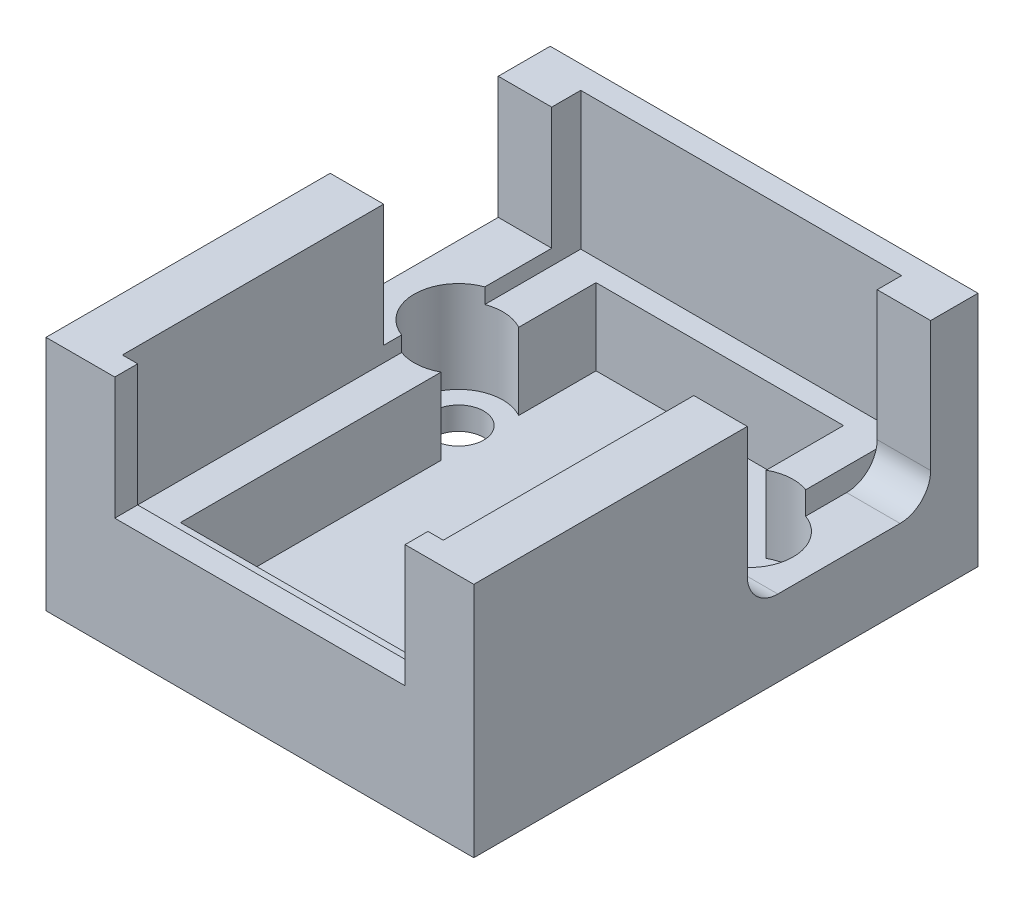
SolidWorks part; units mm, degrees
ref_plane "Płaszczyzna przednia" through (0, 0, 0) normal (0, 0, 1) x (1, 0, 0)
ref_plane "Płaszczyzna górna" through (0, 0, 0) normal (0, 1, 0) x (1, 0, 0)
ref_plane "Płaszczyzna prawa" through (0, 0, 0) normal (1, 0, 0) x (0, 0, -1)
sketch "Szkic1" plane through (0, 0, 0) normal (0, 1, 0) x (1, 0, 0)
  line L1 (-14, -16.5) -> (14, -16.5)
  line L2 (-14, -16.5) -> (-14, 16.5)
  line L3 (-14, 16.5) -> (14, 16.5)
  line L4 (14, -16.5) -> (14, 16.5)
  line L5 (-14, -16.5) -> (14, 16.5) construction
  line L6 (-14, 16.5) -> (14, -16.5) construction
  point P0 (0, 0)
  dimension "D1" = 28
  dimension "D2" = 33
extrude "Dodanie-wyciągnięcie1" add sketch "Szkic1" along normal blind 1.5
sketch "Szkic2" plane through (0, 1.5, 0) normal (0, 1, 0) x (1, 0, 0)
  line L0 (-14, 16.5) -> (14, 16.5)
  line L1 (14, 16.5) -> (14, -16.5)
  line L2 (14, -16.5) -> (-14, -16.5)
  line L3 (-14, -16.5) -> (-14, 16.5)
  line L5 (-10.5, -15) -> (10.5, -15)
  line L6 (-10.5, -15) -> (-10.5, 15)
  line L7 (-10.5, 15) -> (10.5, 15)
  line L8 (10.5, -15) -> (10.5, 15)
  line L9 (-10.5, -15) -> (10.5, 15) construction
  line L10 (-10.5, 15) -> (10.5, -15) construction
  point P4 (0, 0)
  dimension "D1" = 1.5
  dimension "D2" = 3.5
  dimension "D3" = 3.5
  dimension "D4" = 1.5
extrude "Dodanie-wyciągnięcie2" add sketch "Szkic2" along normal blind 14
sketch "Szkic7" plane through (0, 1.5, 0) normal (0, 1, 0) x (1, 0, 0)
  line L1 (-10.5, -15) -> (10.5, -15)
  line L2 (-10.5, -15) -> (-10.5, 15)
  line L3 (-10.5, 15) -> (10.5, 15)
  line L4 (10.5, -15) -> (10.5, 15)
  line L5 (-10.5, -15) -> (10.5, 15) construction
  line L6 (-10.5, 15) -> (10.5, -15) construction
  line L7 (-8.1, -13.6) -> (8.1, -13.6)
  line L8 (-8.1, -13.6) -> (-8.1, 13.6)
  line L9 (-8.1, 13.6) -> (8.1, 13.6)
  line L10 (8.1, -13.6) -> (8.1, 13.6)
  line L11 (-8.1, -13.6) -> (8.1, 13.6) construction
  line L12 (-8.1, 13.6) -> (8.1, -13.6) construction
  point P0 (0, 0)
  point P7 (0, 0)
  dimension "D1" = 1.4
  dimension "D2" = 2.4
extrude "Dodanie-wyciągnięcie4" add sketch "Szkic7" along normal blind 5
sketch "Szkic3" plane through (14, 0, 0) normal (1, 0, 0) x (0, 0, -1)
  line L0 (16.5, 0) -> (16.5, 5) construction
  line L1 (16.5, 15.5) -> (16.5, 0) construction
  line L2 (16.5, 5) -> (13.4, 5) construction
  line L3 (13.4, 5) -> (1.4, 5)
  line L4 (1.4, 5) -> (1.4, 15.5)
  line L5 (-16.5, 15.5) -> (16.5, 15.5) construction
  line L6 (1.4, 15.5) -> (13.4, 15.5)
  line L7 (13.4, 15.5) -> (13.4, 5)
  dimension "D1" = 3.1
  dimension "D2" = 12
  dimension "D3" = 5
extrude "Wytnij-wyciągnięcie1" cut sketch "Szkic3" against normal up to surface (3.5 mm away) contours L3 L4 L6 L7 up to face at (10.5, 11, 0)
sketch "Szkic4" plane through (0, 0, 16.5) normal (0, 0, 1) x (1, 0, 0)
  line L0 (14, 0) -> (14, 7.5) construction
  line L1 (-14, 0) -> (14, 0) construction
  line L2 (14, 15.5) -> (14, 0) construction
  line L3 (14, 7.5) -> (9.5, 7.5) construction
  line L4 (9.5, 7.5) -> (9.5, 15.5)
  line L5 (-14, 15.5) -> (14, 15.5) construction
  line L6 (9.5, 15.5) -> (-9.5, 15.5)
  line L7 (-9.5, 15.5) -> (-9.5, 7.5)
  line L8 (-9.5, 7.5) -> (9.5, 7.5)
  line L9 (-14, 15.5) -> (-14, 0) construction
  dimension "D1" = 4.5
  dimension "D2" = 4.5
  dimension "D3" = 7.5
extrude "Wytnij-wyciągnięcie2" cut sketch "Szkic4" against normal up to surface (1.5 mm away) up to face at (0, 11, 15)
sketch "Szkic5" plane through (-14, 0, 0) normal (-1, 0, 0) x (0, 0, 1)
  line L0 (-16.5, 0) -> (-16.5, 7.5) construction
  line L1 (-16.5, 0) -> (16.5, 0) construction
  line L2 (-16.5, 15.5) -> (-16.5, 0) construction
  line L3 (-16.5, 7.5) -> (-13.1, 7.5) construction
  line L4 (-13.1, 7.5) -> (-13.1, 15.5)
  line L5 (-13.1, 15.5) -> (-2.1, 15.5)
  line L6 (-2.1, 15.5) -> (-2.1, 7.5)
  line L7 (-2.1, 7.5) -> (-13.1, 7.5)
  line L8 (-16.5, 15.5) -> (16.5, 15.5) construction
  dimension "D1" = 3.4
  dimension "D2" = 7.5
  dimension "D3" = 11
extrude "Wytnij-wyciągnięcie3" cut sketch "Szkic5" against normal up to surface (3.5 mm away) up to face at (-10.5, 11, 0)
sketch "Szkic8" plane through (0, 0, 0) normal (0, -1, 0) x (1, 0, 0)
  line L0 (0, 0) -> (0, -6) construction
  line L1 (-9.5, -6) -> (9.5, -6) construction
  circle A0 centre (9.5, -6) radius 1.65
  circle A1 centre (-9.5, -6) radius 1.65
  point P6 (0, -6)
  dimension "D3" = 3.3
  dimension "D1" = 6
  dimension "D2" = 19
extrude "Wytnij-wyciągnięcie4" cut sketch "Szkic8" against normal through all
sketch "Szkic9" plane through (0, 0, 0) normal (0, -1, 0) x (1, 0, 0)
  line L0 (0, 0) -> (0, -4.7269) construction
  circle A0 centre (-9.5, -6) radius 2.9
  circle A1 centre (9.5, -6) radius 2.9
  dimension "D1" = 5.8
extrude "Wytnij-wyciągnięcie8" cut sketch "Szkic9" against normal through all from surface starting at face at (0, 1.5, -3)
fillet "Zaokrąglenie1" radius 2 2 edges at (12.25, 5, -1.4) (12.25, 5, -13.4)
